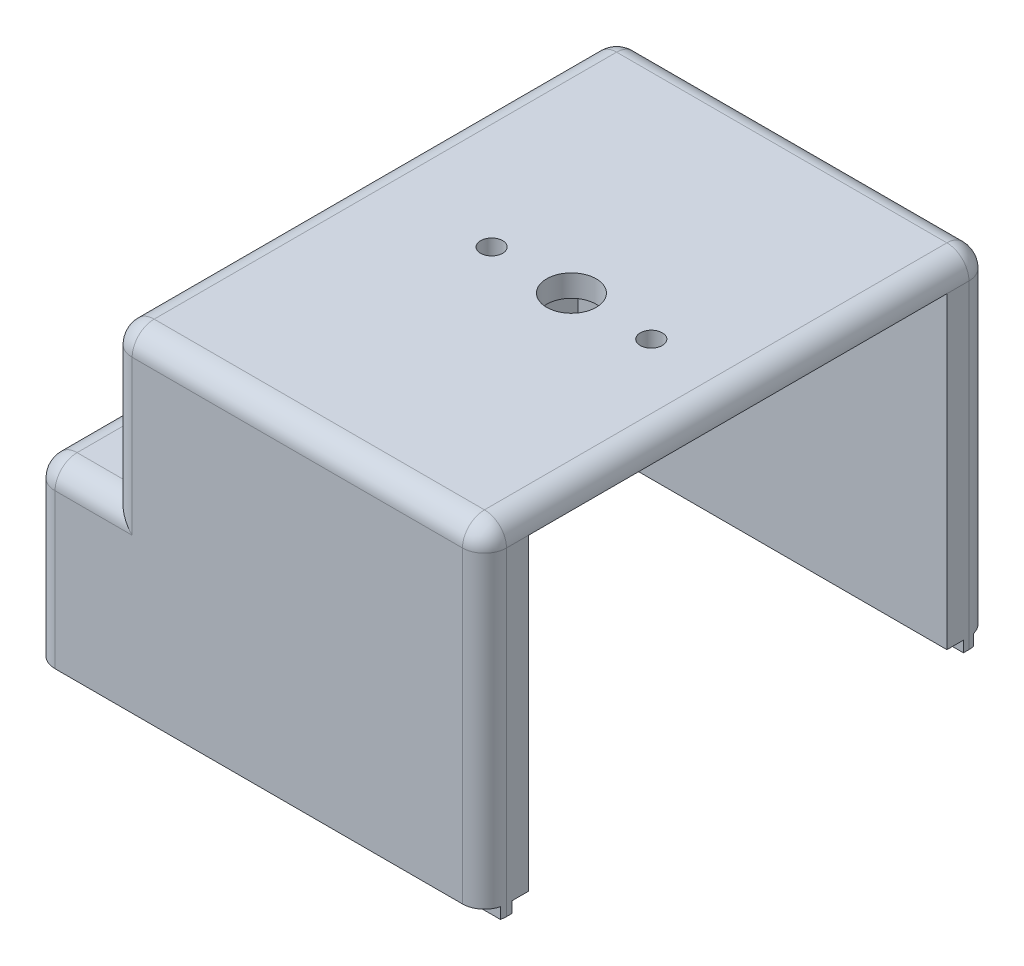
SolidWorks part; units mm, degrees
ref_plane "Plan de face" through (0, 0, 0) normal (0, 0, 1) x (1, 0, 0)
ref_plane "Plan de dessus" through (0, 0, 0) normal (0, 1, 0) x (1, 0, 0)
ref_plane "Plan de droite" through (0, 0, 0) normal (1, 0, 0) x (0, 0, -1)
sketch "Esquisse1" plane through (0, 0, 0) normal (0, 1, 0) x (1, 0, 0)
  line L0 (0, 0) -> (-20.5, 0) construction
  line L1 (20.5, -23) -> (-20.5, -23)
  line L2 (20.5, -23) -> (20.5, 23)
  line L3 (20.5, 23) -> (-20.5, 23)
  line L4 (-20.5, -23) -> (-20.5, 23)
  line L5 (20.5, -23) -> (-20.5, 23) construction
  line L6 (20.5, 23) -> (-20.5, -23) construction
  line L7 (-1.85, 0) -> (12.65, 0) construction
  circle A0 centre (5.4, 0) radius 2.25
  circle A1 centre (-1.85, 0) radius 1
  circle A2 centre (12.65, 0) radius 1
  point P0 (0, 0)
  dimension "D3" = 4.5
  dimension "D5" = 2
  dimension "D6" = 2
  dimension "D1" = 41
  dimension "D2" = 46
  dimension "D4" = 25.9
  dimension "D7" = 14.5
extrude "Boss.-Extru.1" add sketch "Esquisse1" along normal blind 30
sketch "Esquisse2" plane through (0, 0, 0) normal (0, 1, 0) x (1, 0, 0)
  line L0 (-20.5, -23) -> (20.5, -23) construction
  line L1 (-13.5, -23) -> (-20.5, -23)
  line L2 (-13.5, -23) -> (-13.5, 23)
  line L3 (-13.5, 23) -> (-20.5, 23)
  line L4 (-20.5, -23) -> (-20.5, 23)
  line L5 (-13.5, -23) -> (-20.5, 23) construction
  line L6 (-13.5, 23) -> (-20.5, -23) construction
  line L7 (-20.5, 23) -> (-20.5, -23) construction
  line L8 (20.5, 23) -> (-20.5, 23) construction
  line L9 (20.5, -23) -> (20.5, 23) construction
  circle A0 centre (-17, -8.75) radius 3
  circle A1 centre (-17, 8.75) radius 3
  point P0 (-17, 0)
  dimension "D2" = 6
  dimension "D3" = 6
  dimension "D1" = 7
  dimension "D4" = 8.75
  dimension "D5" = 17.5
  dimension "D6" = 37.5
  dimension "D7" = 37.5
extrude "Enlèv. mat.-Extru.1" cut sketch "Esquisse2" against normal blind 14 from surface contours L1 L4 L3 L2 starting at face at (-1.85, 30, 1)
extrude "Enlèv. mat.-Extru.3" cut sketch "Esquisse2<3>" along normal through all both and the other way through all from surface contours A1 | A0 starting at face at (-17, 16, 0)
sketch "Esquisse2<3>" plane through (0, 0, 0) normal (0, 1, 0) x (1, 0, 0) same geometry as "Esquisse2"
sketch "Esquisse3" plane through (0, 0, 0) normal (0, 1, 0) x (1, 0, 0)
  line L1 (20.5, -19) -> (-13, -19)
  line L2 (20.5, -19) -> (20.5, 19)
  line L3 (20.5, 19) -> (-13, 19)
  line L4 (-13, -19) -> (-13, 19)
  line L5 (20.5, -19) -> (-13, 19) construction
  line L6 (20.5, 19) -> (-13, -19) construction
  line L7 (-13.5, -23) -> (-13.5, 23) construction
  line L10 (20.5, -23) -> (20.5, 23) construction
  line L11 (20.5, 23) -> (-13.5, 23) construction
  line L12 (-13.5, -23) -> (20.5, -23) construction
  point P0 (3.75, 0)
  dimension "D1" = 0.5
  dimension "D2" = 4
  dimension "D3" = 4
extrude "Enlèv. mat.-Extru.4" cut sketch "Esquisse3" along normal blind 28
sketch "Esquisse4" plane through (0, 0, 0) normal (0, 1, 0) x (1, 0, 0)
  line L0 (-20.5, 0) -> (20.5, 0) construction
  line L1 (20.5, -20.5012) -> (-9.5, -20.5012)
  line L2 (20.5, -20.5012) -> (20.5, -21.4988)
  line L3 (20.5, -21.4988) -> (-9.5, -21.4988)
  line L4 (-9.5, -20.5012) -> (-9.5, -21.4988)
  line L5 (20.5, -20.5012) -> (-9.5, -21.4988) construction
  line L6 (20.5, -21.4988) -> (-9.5, -20.5012) construction
  line L7 (-20.5, -23) -> (-20.5, 23) construction
  line L8 (20.5, -23) -> (20.5, 23) construction
  line L9 (-13.5, -23) -> (20.5, -23) construction
  line L10 (20.5, 20.5012) -> (20.5, 21.4988)
  line L11 (-9.5, 20.5012) -> (-9.5, 21.4988)
  line L12 (20.5, 21.4988) -> (-9.5, 21.4988)
  line L13 (20.5, 20.5012) -> (-9.5, 20.5012)
  point P0 (5.5, -21)
  dimension "D1" = 0.9975
  dimension "D2" = 2
  dimension "D3" = 30
extrude "Boss.-Extru.2" add sketch "Esquisse4" against normal blind 1
fillet "Congé1" radius 2 10 edges at (-20.5, 8, 23) (-20.5, 8, -23) (-17, 16, 23) (-20.5, 16, 0) (-17, 16, -23) (-13.5, 23, -23) (-13.5, 23, 23) (3.5, 30, -23) (-13.5, 30, 0) (3.5, 30, 23)
fillet "Congé2" radius 2 5 edges at (20.5, 14, 23) (20.5, 29.4142, 22.4142) (20.5, 14, -23) (20.5, 29.4142, -22.4142) (20.5, 30, 0)
